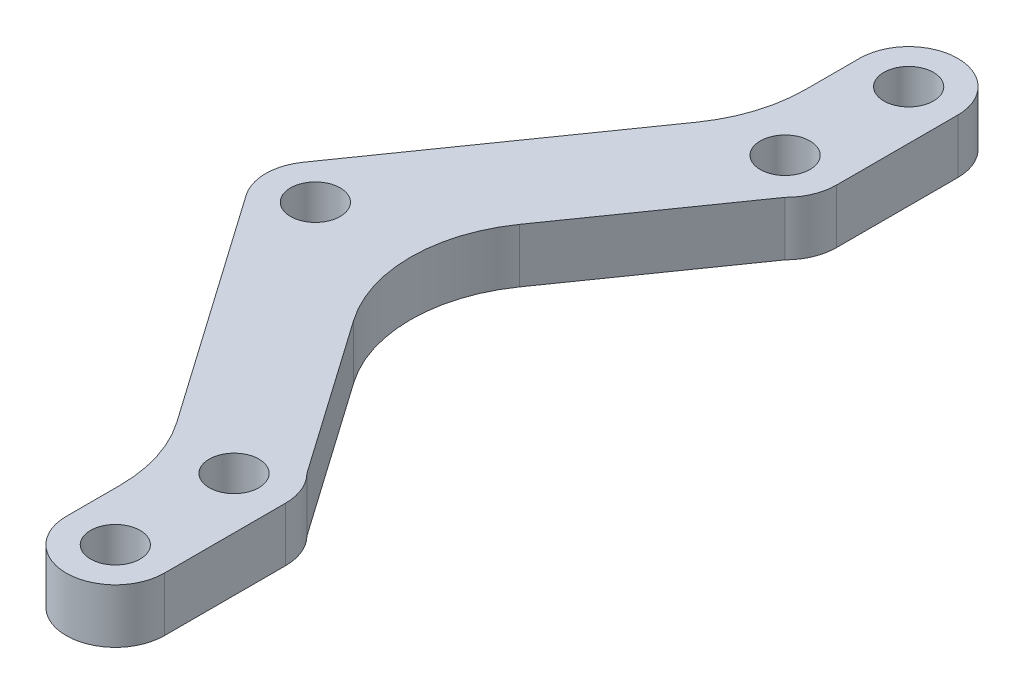
SolidWorks part; units mm, degrees
ref_plane "Front Plane" through (0, 0, 0) normal (0, 0, 1) x (1, 0, 0)
ref_plane "Top Plane" through (0, 0, 0) normal (0, 1, 0) x (1, 0, 0)
ref_plane "Right Plane" through (0, 0, 0) normal (1, 0, 0) x (0, 0, -1)
sketch "Sketch1" plane through (0, 0, 0) normal (0, 1, 0) x (1, 0, 0)
  line L1 (-15.25, -15.25) -> (15.25, -15.25) construction
  line L2 (-15.25, -15.25) -> (-15.25, 15.25) construction
  line L3 (-15.25, 15.25) -> (15.25, 15.25) construction
  line L4 (15.25, -15.25) -> (15.25, 15.25) construction
  line L5 (-15.25, -15.25) -> (15.25, 15.25) construction
  line L6 (-15.25, 15.25) -> (15.25, -15.25) construction
  point P0 (0, 0)
  point P6 (0, 0)
  dimension "D1" = 30.5
sketch "Sketch5" plane through (0, 0, 0) normal (0, 1, 0) x (1, 0, 0)
  line L0 (0, -16) -> (0, 16)
  line L1 (0, 16) -> (-23, 16)
  line L2 (-23, 16) -> (-23, -16)
  line L3 (-23, -16) -> (0, -16)
  line L4 (-11.5, 16) -> (-11.5, -16) construction
  line L5 (-23, 0) -> (0, 0) construction
  point P4 (0, 0)
  point P5 (0, 0)
  point P10 (-15.25, -14.7545)
  point P11 (0, 0)
  point P13 (0, 0)
  point P14 (-15.25, 0)
  point P17 (-15.25, 0)
  dimension "D1" = 23
  dimension "D2" = 32
sketch "Sketch6" plane through (0, 0, 0) normal (0, 1, 0) x (-1, 0, 0)
  line L14 (23, -16) -> (23, 16) construction
  line L20 (23, -16) -> (23, 16) construction
  line L22 (23, 0) -> (0, 0) construction
  circle A2 centre (26, 0) radius 1.375 construction
  point P9 (29.75, 0)
  point P10 (0, 0)
  point P17 (29.75, 0)
  dimension "D7" = 3
  dimension "D8" = 2.75
sketch "Sketch2" plane through (0, 0, 0) normal (0, 1, 0) x (1, 0, 0)
  line L0 (-15.25, 15.25) -> (15.25, -15.25) construction
  line L7 (-27.375, 0) -> (-28.75, 0)
  line L8 (-15.25, 15.25) -> (-16.1391, 13.9802) construction
  line L11 (-13.2335, 13.2335) -> (-22.5, 0)
  line L12 (-17.8346, 16.4553) -> (-28.2526, 1.5774)
  line L13 (-12.3982, 15.25) -> (-12.3982, 21.9553)
  line L14 (-17.8346, 16.4553) -> (-17.8346, 21.9553)
  line L15 (-22.5, 0) -> (-24.625, 0)
  line L17 (-12.3982, 21.9553) -> (-17.8346, 21.9553) construction
  arc A0 (-28.2526, 1.5774) -> (-28.75, 0) centre (-26, 0) ccw
  arc A1 (-24.625, 0) -> (-27.375, 0) centre (-26, 0) ccw
  arc A3 (-13.2335, 13.2335) -> (-12.3982, 15.25) centre (-15.25, 15.25) ccw
  arc A4 (-12.3982, 21.9553) -> (-17.8346, 21.9553) centre (-15.1164, 21.9553) ccw
  point P5 (-29.75, 0)
  dimension "D4" = 5.5
  dimension "D5" = 2.75
  dimension "D1" = 3.5
  dimension "D3" = 5.5
extrude "Boss-Extrude1" add sketch "Sketch2" along normal blind 3
sketch "Sketch3" plane through (0, 3, 0) normal (0, 1, 0) x (1, 0, 0)
  circle A0 centre (-15.25, 15.25) radius 1.375
  arc A1 (-24.625, 0) -> (-27.375, 0) centre (-26, 0) ccw construction
  circle A2 centre (-15.1164, 21.9553) radius 1.375
extrude "Cut-Extrude1" cut sketch "Sketch3" against normal through all
mirror "Mirror2" about plane through (-22.5, 3, 0) normal (0, 0, -1) of "Cut-Extrude1", "Boss-Extrude1"
fillet "Fillet1" radius 8 3 edges at (-22.5, 1.5, 0) (-17.8346, 1.5, 16.4553) (-17.8346, 1.5, -16.4553)
